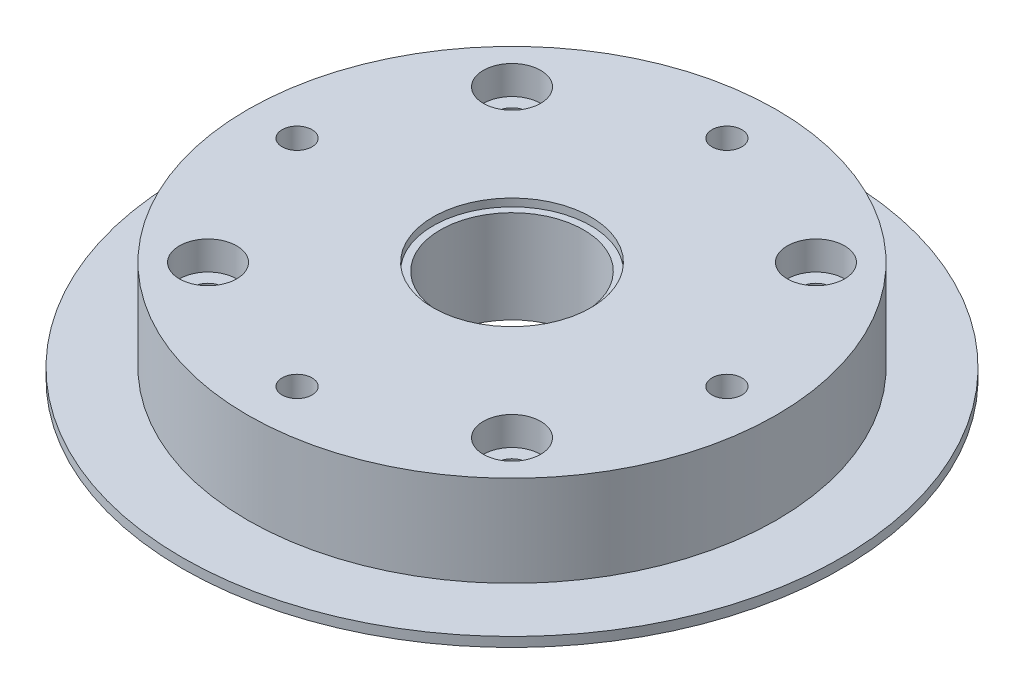
SolidWorks part; units mm, degrees
ref_plane "Front Plane" through (0, 0, 0) normal (0, 0, 1) x (1, 0, 0)
ref_plane "Top Plane" through (0, 0, 0) normal (0, 1, 0) x (1, 0, 0)
ref_plane "Right Plane" through (0, 0, 0) normal (1, 0, 0) x (0, 0, -1)
sketch "Sketch1" plane through (0, 0, 0) normal (0, 1, 0) x (1, 0, 0)
  line L0 (0, 0) -> (22.5, 0) construction
  circle A0 centre (0, 0) radius 34.5
  circle A1 centre (22.5, 0) radius 1.5635
  circle A2 centre (15.9099, -15.9099) radius 1.5635
  circle A3 centre (0, -22.5) radius 1.5635
  circle A4 centre (-15.9099, -15.9099) radius 1.5635
  circle A5 centre (-22.5, 0) radius 1.5635
  circle A6 centre (-15.9099, 15.9099) radius 1.5635
  circle A7 centre (0, 22.5) radius 1.5635
  circle A8 centre (15.9099, 15.9099) radius 1.5635
  circle A9 centre (0, 0) radius 8.25
  circle A10 centre (0, 0) radius 27.69
  circle A11 centre (0, 0) radius 7.5
  point P14 (0, 0)
  dimension "D2" = 69
  dimension "D3" = 16.5
  dimension "D5" = 3.127
  dimension "D6" = 55.38
  dimension "D7" = 15
  dimension "D4" = 22.5
  dimension "D1" = 8
extrude "Boss-Extrude1" add sketch "Sketch1" against normal blind 1 contours A0 A10 | A10 A2 A3 A4 A5 A6 A7 A8 A9 A1 | A11 A9 region at (-33.5242, 0, 0) region at (-8.0167, 0, 0) region at (-26.9068, 0, 0)
extrude "Boss-Extrude2" add sketch "Sketch1<3>" along normal blind 9.525 contours A10 A2 A3 A4 A5 A6 A7 A8 A9 A1 | A11 A9 region at (-8.0167, 0, 0) region at (-26.9068, 0, 0)
sketch "Sketch1<3>" plane through (0, 0, 0) normal (0, 1, 0) x (1, 0, 0) same geometry as "Sketch1"
sketch "Sketch2" plane through (0, 9.525, 0) normal (0, 1, 0) x (1, 0, 0)
  circle A0 centre (15.9099, 15.9099) radius 3
  circle A1 centre (15.9099, -15.9099) radius 3
  circle A2 centre (-15.9099, -15.9099) radius 3
  circle A3 centre (-15.9099, 15.9099) radius 3
  point P12 (0, 0)
  circle M4 centre (-15.9099, -15.9099) radius 1.5635
  circle M6 centre (-15.9099, 15.9099) radius 1.5635
  circle M8 centre (15.9099, 15.9099) radius 1.5635
  dimension "D1" = 6
  dimension "D2" = 4
extrude "Cut-Extrude1" cut sketch "Sketch2" against normal blind 3 contours A3 M6 | A0 M8 | A2 M4 | A1 region at (12.9948, 9.525, -15.9099) region at (-18.825, 9.525, 15.9099) region at (-18.825, 9.525, -15.9099)
sketch "Sketch3" plane through (0, -1, 0) normal (0, -1, 0) x (1, 0, 0)
  circle A0 centre (22.5, 0) radius 1.925
  circle A1 centre (0, -22.5) radius 1.925
  circle A2 centre (-22.5, 0) radius 1.925
  circle A3 centre (0, 22.5) radius 1.925
  point P12 (0, 0)
  dimension "D1" = 3.85
  dimension "D2" = 4
extrude "Cut-Extrude2" cut sketch "Sketch3" against normal blind 4
extrude "Cut-Extrude3" cut sketch "Sketch1<6>" against normal blind 0.8 from offset 9.525 contours A11 A9 region at (-8.0167, 0, 0)
sketch "Sketch1<6>" plane through (0, 0, 0) normal (0, 1, 0) x (1, 0, 0) same geometry as "Sketch1"
equation "\"D1@Boss-Extrude2\"=\"sheetThickness\"*2"
equation "\"largeBearOD\"= 21mm"
equation "\"largeBearID\" = 15mm"
equation "\"largeBearOTight\"= 0.127mm'calibrate - hold onto gears"
equation "\"largeBearITight\"= 0mm'calibrate - hold onto eccentric nut"
equation "\"largeBearFlangeDiam\" = 22.5mm"
equation "\"largeBearFlangeWidth\" = 0.8mm"
equation "\"smallBearOD\"= 15mm"
equation "\"smallBearOTight\"= 0mm'calibrate - hold onto bottom of gearbox"
equation "\"smallBearOLoose\"= 0mm'calibrate - able to take off topHat"
equation "\"smallBearID\" = 10mm"
equation "\"smallBearITight\" = 0mm'hold onto "
equation "\"pinCircleDiam\"= 75mm"
equation "\"pinDiam\"= 6mm"
equation "\"sheetThickness\"= 0.1875in"
equation "\"ballBearDiam\"= 3.214mm"
equation "\"thrustBearingThickness\"= 5mm'measure this irl and change"
equation "\"thrustBearingID\"= 0mm'measure this irl and change"
equation "\"thrustBearingOD\"= 0mm'measure this irl and change"
equation "\"eccentricity\" = 1mm"
equation "\"D7@Sketch1\"=\"smallBearOD\"+\"smallBearOTight\""
equation "\"D19@Cut-Extrude3\"=\"sheetThickness\"*2"
equation "\"D2@Sketch1\"=\"pinCircleDiam\"-\"pinDiam\""
